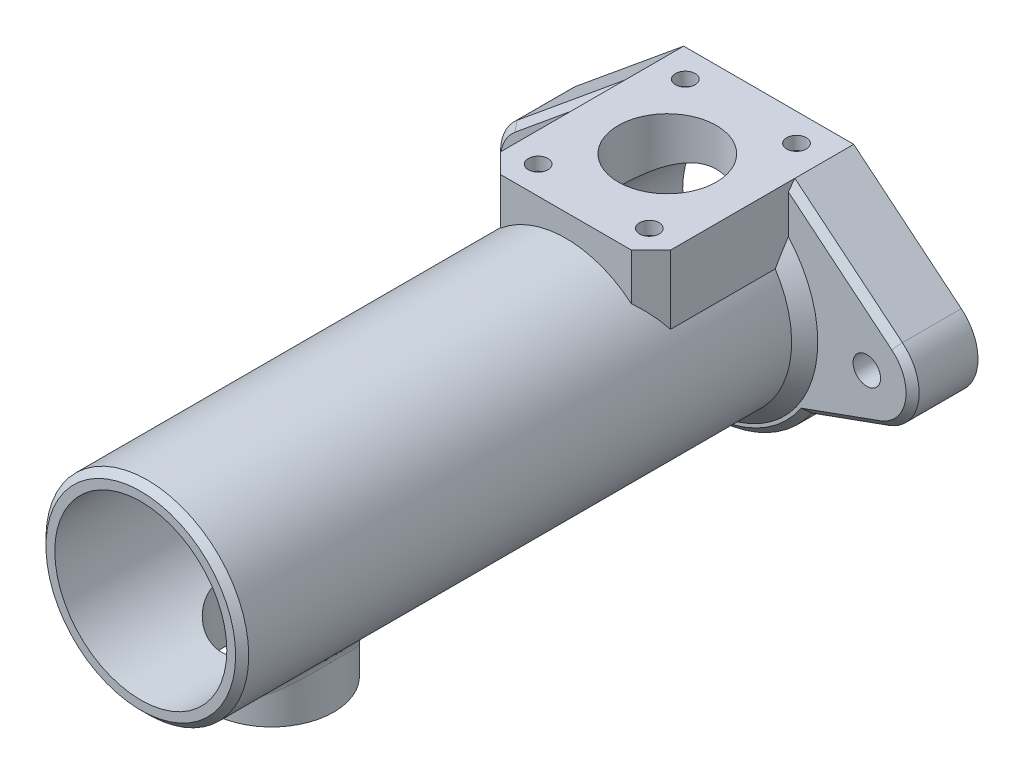
SolidWorks part; units mm, degrees
ref_plane "Ebene vorne" through (0, 0, 0) normal (0, 0, 1) x (1, 0, 0)
ref_plane "Ebene oben" through (0, 0, 0) normal (0, 1, 0) x (1, 0, 0)
ref_plane "Ebene rechts" through (0, 0, 0) normal (1, 0, 0) x (0, 0, -1)
sketch "Skizze1" plane through (0, 0, 0) normal (0, 0, 1) x (1, 0, 0)
  line L0 (0, 0) -> (0, 88.6182) construction
  line L1 (0, 88.6182) -> (0, -16.941) construction
  line L2 (0, -16.941) -> (0, 0) construction
  line L3 (0, 0) -> (13.15, 0) construction
  line L4 (13.15, 0) -> (-13.15, 0) construction
  line L5 (-87.7267, 0) -> (-15.5, 0) construction
  line L6 (-13.15, 0) -> (0, 0) construction
  line L8 (-13, 8.441) -> (-13, 18.941)
  line L9 (-13, 18.941) -> (13, 18.941)
  line L10 (13, 8.441) -> (13, 18.941)
  line L15 (-15.5, 0) -> (-87.7267, 0) construction
  circle A0 centre (0, 0) radius 13.15
  arc A4 (-13, 8.441) -> (13, 8.441) centre (0, 0) ccw
  dimension "D1" = 26.3
  dimension "D2" = 31
  dimension "D3" = 10.5
  dimension "D4" = 26
  dimension "D5" = 13
  dimension "D9" = 18.941
extrude "Grundkörper" add sketch "Skizze1" along normal blind 96
sketch "Skizze11" plane through (0, 0, 0) normal (0, 0, -1) x (-1, 0, 0)
  line L0 (0, 0) -> (25, 0) construction
  line L1 (0, 0) -> (0, 18.941) construction
  line L2 (-13, 18.941) -> (13, 18.941) construction
  line L3 (13, 18.941) -> (29.4481, 5.4051)
  line L4 (15.604, -10.8405) -> (27.38, -6.583)
  line L5 (-15.604, -10.8405) -> (-27.38, -6.583)
  line L6 (-13, 18.941) -> (-29.4481, 5.4051)
  line L7 (-13, 18.941) -> (13, 18.941)
  circle A0 centre (25, 0) radius 2.1
  arc A1 (27.38, -6.583) -> (29.4481, 5.4051) centre (25, 0) ccw
  arc A2 (-13, 8.441) -> (13, 8.441) centre (0, 0) ccw construction
  arc A3 (-27.38, -6.583) -> (-29.4481, 5.4051) centre (-25, 0) cw
  circle A4 centre (0, 0) radius 13.15
  circle A5 centre (0, 0) radius 13.15 construction
  circle A6 centre (-25, 0) radius 2.1
  arc A7 (-15.604, -10.8405) -> (15.604, -10.8405) centre (0, 0) ccw
  arc A8 (1.4965, 18.941) -> (-1.4965, 18.941) centre (0, 0) ccw
  arc M6 (-13, 8.441) -> (13, 8.441) centre (0, 0) ccw
  line M7 (13, 8.441) -> (13, 18.941)
  line M8 (13, 18.941) -> (-13, 18.941)
  line M9 (-13, 18.941) -> (-13, 8.441)
  circle M10 centre (0, 0) radius 13.15
  dimension "D1" = 4.2
  dimension "D2" = 14
  dimension "D4" = 38
  dimension "D3" = 50
extrude "Aufsatz-Linear austragen1" add sketch "Skizze11" against normal blind 10 contours A3 L5 L6 A6 M6 M9 | M9 M6 M7 M8 M10 | L4 A1 L3 A0 M7 M6 region at (-12.5366, 13.691, 0) region at (-20.7513, 11.5985, 0)
sketch "Skizze2" plane through (0, 0, 96) normal (0, 0, 1) x (1, 0, 0)
  line L1 (-13, 18.941) -> (13, 18.941)
  line L2 (-13, 18.941) -> (-13, 8.441)
  line L4 (13, 18.941) -> (13, 8.441)
  arc A1 (13, 8.441) -> (-13, 8.441) centre (0, 0) ccw
extrude "FlanschTrichter" cut sketch "Skizze2" against normal blind 65
sketch "Skizze3" plane through (0, 0, 0) normal (0, 0, -1) x (-1, 0, 0)
  line L0 (-13, 18.941) -> (13, 18.941) construction
  line L1 (-12.9249, 18.941) -> (13.0751, 18.941)
  line L2 (-12.9249, 18.941) -> (-12.9249, 2.4228)
  line L4 (13.0751, 18.941) -> (13.0751, 1.4014)
  arc A0 (13.0751, 1.4014) -> (-12.9249, 2.4228) centre (0, 0) ccw
  circle A1 centre (0, 0) radius 13.15 construction
sketch "Skizze7" plane through (0, 0, 0) normal (0, 1, 0) x (1, 0, 0)
  line L0 (-15.5, -96) -> (15.5, -96) construction
  line L1 (0, 0) -> (0, -96) construction
  circle A0 centre (0, -76) radius 7.5
  dimension "D2" = 15
  dimension "D1" = 20
extrude "FutterAusgang" cut sketch "Skizze7" against normal through all
ref_plane "Ebene1" through (0, -20, 0) normal (0, 1, 0) x (1, 0, 0)
sketch "Skizze8" plane through (0, -20, 0) normal (0, 1, 0) x (1, 0, 0)
  circle A0 centre (0, -76) radius 7.5 construction
  circle A1 centre (0, -76) radius 7.5
  circle A2 centre (0, -76) radius 9.5
  dimension "D1" = 2
extrude "FutterAusgangRohr" add sketch "Skizze8" along normal up to next
sketch "Skizze9" plane through (0, 18.941, 0) normal (0, 1, 0) x (1, 0, 0)
  line L0 (0, -31) -> (0, 0) construction
  line L1 (0, -8) -> (0, -23) construction
  line L2 (13, 0) -> (13, -31) construction
  line L3 (13, -31) -> (0, -31) construction
  line L4 (-13, -31) -> (-13, 0) construction
  line L5 (-13, 0) -> (13, 0) construction
  line L6 (0, -31) -> (0, -34.0754) construction
  line L7 (0, 0) -> (9.9805, 0) construction
  line L8 (9.9805, 0) -> (9.9805, -31) construction
  line L9 (9.9805, -31) -> (-9.3479, -31) construction
  line L10 (13, -31) -> (-13, -31) construction
  line L11 (-9.3479, -31) -> (-9.3479, 0) construction
  circle A0 centre (0, -15.5) radius 7.5
  circle A3 centre (8.5, -4.25) radius 1.5
  circle A4 centre (8.5, -26.75) radius 1.5
  circle A6 centre (-8.5, -4.25) radius 1.5
  circle A7 centre (-8.5, -26.75) radius 1.5
  dimension "D1" = 15
  dimension "D3" = 3
  dimension "D4" = 11.25
  dimension "D6" = 8.5
  dimension "D2" = 3
  dimension "D5" = 11.25
  dimension "D7" = 8.5
extrude "Schraubenbohrungen" cut sketch "Skizze9" against normal blind 4
sketch "Skizze15" plane through (0, 14.941, 0) normal (0, 1, 0) x (1, 0, 0)
  circle A0 centre (0, -15.5) radius 7.5
  dimension "D1" = 15
extrude "Bohrung 15mm" cut sketch "Skizze15" against normal up to next and the other way through all
sketch "Skizze14" plane through (0, 14.941, 0) normal (0, 1, 0) x (1, 0, 0)
  line L0 (8.5, -4.25) -> (11.7952, -4.25) construction
  line L1 (11.7952, -4.25) -> (4.2709, -4.25) construction
  line L2 (4.2709, -4.25) -> (8.5, -4.25) construction
  line L3 (8.5, -4.25) -> (8.5, -8.7633) construction
  line L4 (8.5, -8.7633) -> (8.5, -1.041) construction
  line L5 (0, 0) -> (0, -33.0627) construction
  line L6 (6.3557, -7.9642) -> (10.6444, -7.9641)
  line L7 (10.6444, -7.9641) -> (12.7887, -4.25)
  line L8 (12.7887, -4.25) -> (10.6443, -0.5358)
  line L9 (10.6443, -0.5358) -> (6.3556, -0.5359)
  line L10 (6.3556, -0.5359) -> (4.2113, -4.25)
  line L11 (4.2113, -4.25) -> (6.3557, -7.9642)
  line L12 (0, -33.0627) -> (0, -15.5) construction
  line L13 (0, -15.5) -> (17.026, -15.5) construction
  line L14 (17.026, -15.5) -> (-15.5, -15.5) construction
  line L15 (-15.5, -10) -> (-15.5, -96) construction
  line L16 (-6.3556, -0.5359) -> (-4.2113, -4.25)
  line L17 (-4.2113, -4.25) -> (-6.3557, -7.9642)
  line L18 (-6.3557, -7.9642) -> (-10.6444, -7.9641)
  line L19 (-10.6444, -7.9641) -> (-12.7887, -4.25)
  line L20 (-12.7887, -4.25) -> (-10.6443, -0.5358)
  line L21 (-10.6443, -0.5358) -> (-6.3556, -0.5359)
  line L22 (6.3557, -23.0358) -> (10.6444, -23.0359)
  line L23 (-12.7887, -26.75) -> (-10.6443, -30.4642)
  line L24 (-10.6444, -23.0359) -> (-12.7887, -26.75)
  line L25 (-6.3557, -23.0358) -> (-10.6444, -23.0359)
  line L26 (-4.2113, -26.75) -> (-6.3557, -23.0358)
  line L27 (-10.6443, -30.4642) -> (-6.3556, -30.4641)
  line L28 (-6.3556, -30.4641) -> (-4.2113, -26.75)
  line L29 (10.6444, -23.0359) -> (12.7887, -26.75)
  line L30 (12.7887, -26.75) -> (10.6443, -30.4642)
  line L31 (10.6443, -30.4642) -> (6.3556, -30.4641)
  line L32 (6.3556, -30.4641) -> (4.2113, -26.75)
  line L33 (4.2113, -26.75) -> (6.3557, -23.0358)
  circle A0 centre (8.5, -4.25) radius 3.7141 construction
  circle A2 centre (-8.5, -4.25) radius 3.7141 construction
  circle A3 centre (-8.5, -26.75) radius 3.7141 construction
  circle A4 centre (8.5, -26.75) radius 3.7141 construction
  circle A5 centre (8.5, -26.75) radius 1.5 construction
  dimension "D1" = 4.2887
extrude "Mutter " add sketch "Skizze14" along normal blind 2
chamfer "Fase1" distance 3 angle 45 2 edges at (13, 13.691, 31) (-13, 13.691, 31)
chamfer "Fase2" distance 2 angle 45 1 edges at (0, -15.5, 10)
fillet "Verrundung1" radius 2 1 edges at (-2.4317, -15.3081, 85.1835)
chamfer "Fase3" distance 1 angle 45 7 edges at (21.224, 12.173, 10) (31.8981, -1.19, 10) (21.492, -8.7117, 10) (0, -19, 10) (-21.492, -8.7117, 10) (-31.8981, -1.19, 10) (-21.224, 12.173, 10)
chamfer "Fase4" distance 1 angle 45 1 edges at (15.5, 0, 96)
